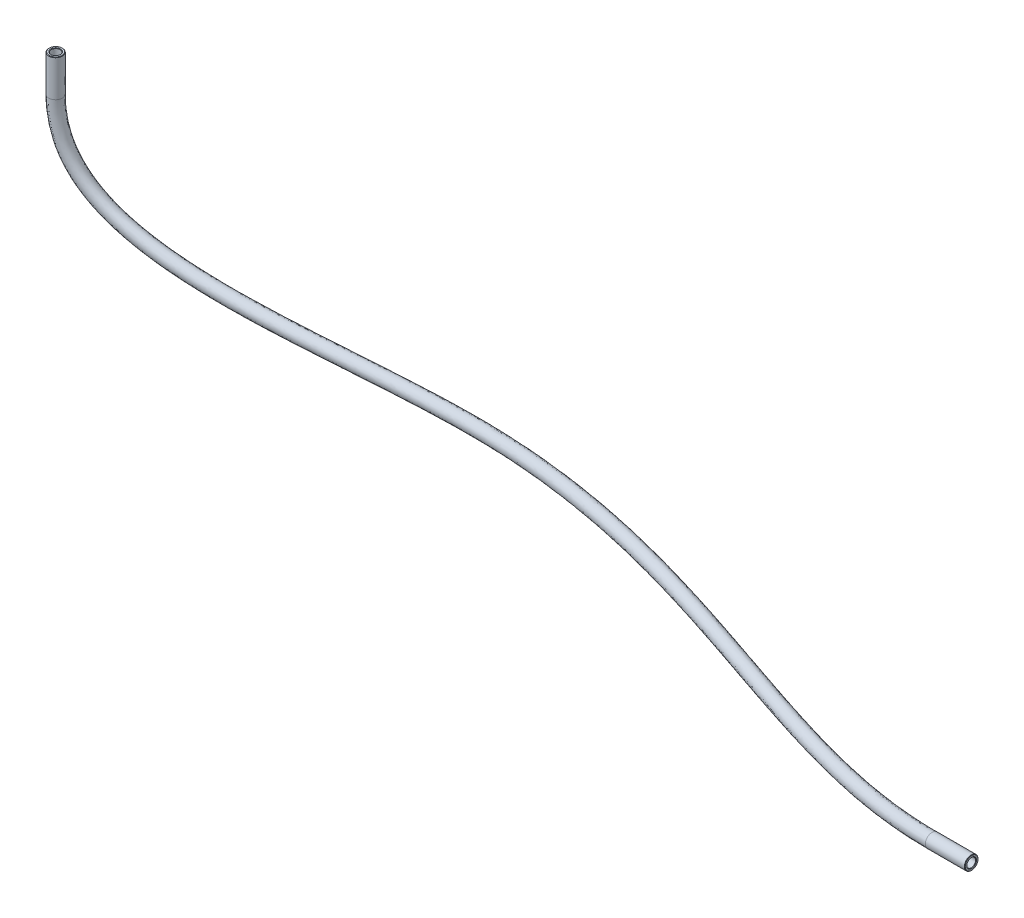
SolidWorks part; units mm, degrees
ref_plane "Front Plane" through (0, 0, 0) normal (0, 0, 1) x (1, 0, 0)
ref_plane "Top Plane" through (0, 0, 0) normal (0, 1, 0) x (1, 0, 0)
ref_plane "Right Plane" through (0, 0, 0) normal (1, 0, 0) x (0, 0, -1)
sketch3d "3DSketch1"
  line L0 (-16.7111, -46.6, -27.0012) -> (-16.7111, -35.8, -27.0012)
  line L1 (249.105, -110.4823, -29.925) -> (237.525, -110.4823, -29.925)
  spline S0 degree 3 poles (237.525, -110.4823, -29.925) (189.0443, -110.4823, -29.925) (128.5489, -81.4079, -64.2742) (-16.7111, -86.7065, -27.0012) (-16.7111, -46.6, -27.0012) knots 0 0 0 0 0.571945 1 1 1 1
sketch "Sketch1" plane through (239.725, 0, 0) normal (-1, 0, 0) x (0, 0, 1)
  circle A0 centre (-29.925, -110.4823) radius 2
  circle A1 centre (-29.925, -110.4823) radius 1.3
  circle A2 centre (-29.925, -110.4823) radius 3.5386 construction
  dimension "D1" = 2.6
  dimension "D2" = 4
sweep "Sweep1" add profiles "Sketch1" path "3DSketch1"
chamfer "Chamfer1" distance 0.127 angle 45 4 edges at (249.105, -112.4823, -29.925) (249.105, -111.7823, -29.925) (-18.5111, -35.8, -26.1293) (-17.8811, -35.8, -26.4345)
